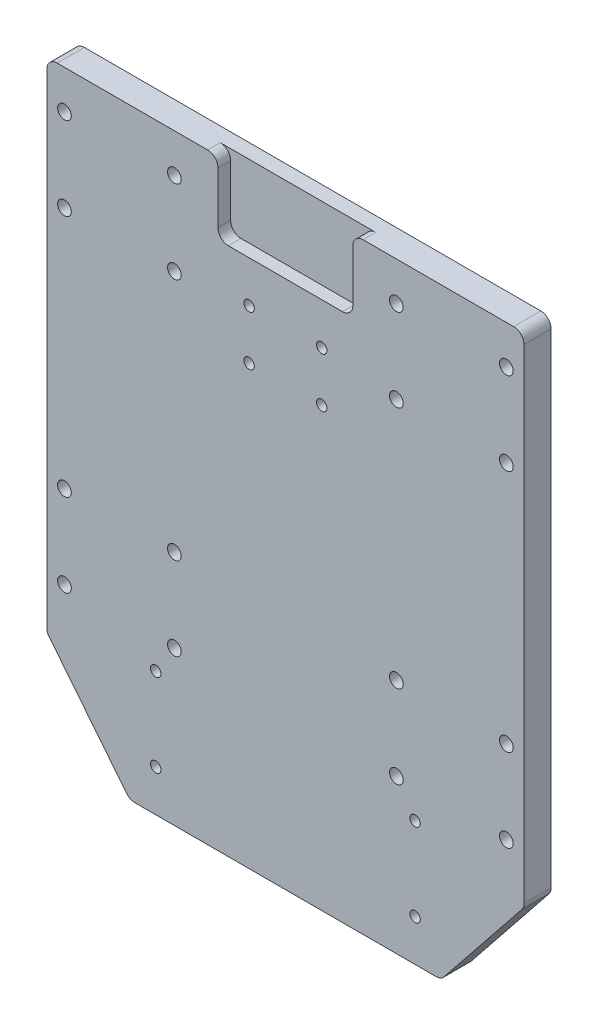
SolidWorks part; units mm, degrees
ref_plane "Front Plane" through (0, 0, 0) normal (0, 0, 1) x (1, 0, 0)
ref_plane "Top Plane" through (0, 0, 0) normal (0, 1, 0) x (1, 0, 0)
ref_plane "Right Plane" through (0, 0, 0) normal (1, 0, 0) x (0, 0, -1)
sketch "Sketch1" plane through (0, 0, 0) normal (0, 0, 1) x (1, 0, 0)
  line L0 (0, 0) -> (0, -170) construction
  line L2 (115, -120) -> (115, 120)
  line L3 (115, 120) -> (-115, 120)
  line L4 (-115, -120) -> (-115, 120)
  line L5 (115, -120) -> (-115, 120) construction
  line L6 (115, 120) -> (-115, -120) construction
  line L7 (75, -170) -> (-75, -170)
  line L11 (-115, -120) -> (115, -120) construction
  line L14 (115, -120) -> (75, -170)
  line L15 (-115, -120) -> (-75, -170)
  point P0 (0, 0)
  dimension "D1" = 240
  dimension "D2" = 230
  dimension "D3" = 40
  dimension "D4" = 50
extrude "Boss-Extrude1" add sketch "Sketch1" along normal blind 13.1
fillet "Fillet1" radius 5 6 edges at (-115, 120, 6.55) (115, 120, 6.55) (75, -170, 6.55) (-75, -170, 6.55) (-115, -120, 6.55) (115, -120, 6.55)
sketch "Sketch2" plane through (0, 0, 13.1) normal (0, 0, 1) x (1, 0, 0)
  line L0 (110, 120) -> (-110, 120) construction
  line L1 (-32.5, 120) -> (32.5, 120)
  line L2 (-32.5, 120) -> (-32.5, 85)
  line L3 (-32.5, 85) -> (32.5, 85)
  line L4 (32.5, 120) -> (32.5, 85)
  line L5 (-32.5, 120) -> (32.5, 85) construction
  line L6 (-32.5, 85) -> (32.5, 120) construction
  line L7 (0, 102.5) -> (0, 0) construction
  point P0 (0, 102.5)
  dimension "D1" = 65
  dimension "D2" = 35
extrude "Cut-Extrude1" cut sketch "Sketch2" against normal through all
fillet "Fillet2" radius 5 4 edges at (32.5, 85, 6.55) (32.5, 120, 6.55) (-32.5, 85, 6.55) (-32.5, 120, 6.55)
sketch "Sketch3" plane through (0, 0, 13.1) normal (0, 0, 1) x (1, 0, 0)
  line L0 (-37.5, 120) -> (-110, 120) construction
  line L1 (-52.1786, 120) -> (57.2952, 120)
  line L2 (-52.1786, 120) -> (-52.1786, 71.0554)
  line L3 (-52.1786, 71.0554) -> (57.2952, 71.0554)
  line L4 (57.2952, 120) -> (57.2952, 71.0554)
extrude "Boss-Extrude2" add sketch "Sketch3" against normal blind 7
sketch "Sketch4" plane through (0, 0, 0) normal (0, 0, -1) x (-1, 0, 0)
  point P0 (53.5, -55.89)
  point P1 (106.5, -55.89)
  point P3 (106.5, -95.89)
  point P5 (53.5, -95.89)
  point P7 (-53.5, -55.89)
  point P9 (-53.5, -95.89)
  point P11 (-106.5, -95.89)
  point P13 (-106.5, -55.89)
  point P15 (-106.5, 101.37)
  point P17 (-53.5, 101.37)
  point P19 (-53.5, 61.37)
  point P21 (-106.5, 61.37)
  point P23 (53.5, 101.37)
  point P25 (53.5, 61.37)
  point P27 (106.5, 101.37)
  point P29 (106.5, 61.37)
  point P31 (62.5, -110)
  point P33 (62.5, -150)
  point P35 (-62.5, -110)
  point P37 (-62.5, -150)
  point P39 (-17.5, 64.95)
  point P41 (-17.5, 40.95)
  point P43 (17.5, 40.95)
  point P45 (17.5, 64.95)
sketch "Sketch5" plane through (0, 0, 13.1) normal (0, 0, 1) x (1, 0, 0)
  circle A0 centre (106.5, 101.37) radius 3.3
  circle A1 centre (53.5, 101.37) radius 3.3
  circle A2 centre (53.5, 61.37) radius 3.3
  circle A3 centre (106.5, 61.37) radius 3.3
  circle A4 centre (-53.5, 101.37) radius 3.3
  circle A5 centre (-106.5, 101.37) radius 3.3
  circle A6 centre (-106.5, 61.37) radius 3.3
  circle A7 centre (-53.5, 61.37) radius 3.3
  circle A8 centre (-106.5, -55.89) radius 3.3
  circle A9 centre (-53.5, -55.89) radius 3.3
  circle A10 centre (-53.5, -95.89) radius 3.3
  circle A11 centre (-106.5, -95.89) radius 3.3
  circle A12 centre (53.5, -55.89) radius 3.3
  circle A13 centre (106.5, -55.89) radius 3.3
  circle A14 centre (106.5, -95.89) radius 3.3
  circle A15 centre (53.5, -95.89) radius 3.3
  dimension "D1" = 6.6
extrude "Cut-Extrude2" cut sketch "Sketch5" against normal through all
sketch "Sketch6" plane through (0, 0, 13.1) normal (0, 0, 1) x (1, 0, 0)
  circle A0 centre (17.5, 64.95) radius 2.5
  circle A1 centre (17.5, 40.95) radius 2.5
  circle A2 centre (-17.5, 64.95) radius 2.5
  circle A3 centre (-17.5, 40.95) radius 2.5
  dimension "D1" = 5
extrude "Cut-Extrude3" cut sketch "Sketch6" against normal through all
sketch "Sketch8" plane through (0, 0, 13.1) normal (0, 0, 1) x (1, 0, 0)
  circle A0 centre (62.5, -110) radius 2.5
  circle A1 centre (62.5, -150) radius 2.5
  circle A2 centre (-62.5, -110) radius 2.5
  circle A3 centre (-62.5, -150) radius 2.5
  dimension "D1" = 5
extrude "Cut-Extrude4" cut sketch "Sketch8" against normal through all
sketch "Sketch9" plane through (0, 0, 13.1) normal (0, 0, 1) x (1, 0, 0)
  circle A0 centre (53.5, -95.89) radius 5.5
  circle A1 centre (-53.5, -95.89) radius 5.5
  dimension "D1" = 11
extrude "Cut-Extrude5" cut sketch "Sketch9" against normal blind 6
move or copy body "Body-Move/Copy1" bodies to move or copy 107 copy no rotation origin (0, 0, 6) rotation axis (0, 1, 0) rotation angle 180
sketch3d "3DSketch1"
  line L0 (-115, 115, -1.1) -> (-115, 120, -1.1) construction
  line L1 (-115, 120, -1.1) -> (-110, 120, -1.1) construction
  line L2 (-115, 120, -1.1) -> (-115, 120, 12) construction
equation "\"M4 Clearence\"= 4.5mm"
equation "\"M6 Threaded\"= 5mm"
equation "\"M6 Clearence\"= 6.6mm"
equation "\"D1@Sketch6\"=\"M6 Threaded\""
equation "\"D1@Sketch5\"=\"M6 Clearence\""
equation "\"D1@Sketch8\"=\"M6 Threaded\""
equation "\"M5 Clearence\"= 5.5mm"
